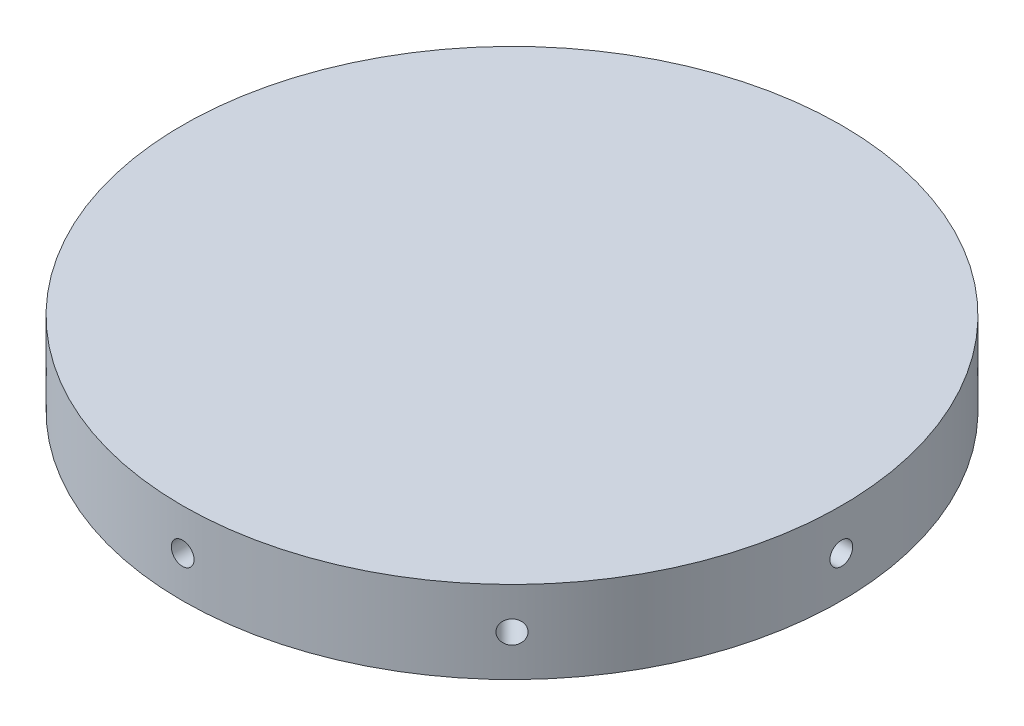
SolidWorks part; units mm, degrees
material "6061 Alloy"
ref_plane "Front Plane" through (0, 0, 0) normal (0, 0, 1) x (1, 0, 0)
ref_plane "Top Plane" through (0, 0, 0) normal (0, 1, 0) x (1, 0, 0)
ref_plane "Right Plane" through (0, 0, 0) normal (1, 0, 0) x (0, 0, -1)
sketch "Sketch1" plane through (0, 0, 0) normal (0, 1, 0) x (1, 0, 0)
  circle A0 centre (0, 0) radius 50.8
  dimension "D1" = 101.6
extrude "Boss-Extrude1" add sketch "Sketch1" along normal blind 12.7
ref_plane "Plane1" through (0, 0, 50.8) normal (0, 0, 1) x (1, 0, 0)
sketch "Sketch2" plane through (0, 0, 50.8) normal (0, 0, 1) x (1, 0, 0)
  line L0 (0, 0) -> (0, 12.7) construction
  line L1 (50.8, 12.7) -> (-50.8, 12.7) construction
  circle A0 centre (0, 6.35) radius 1.7526
  dimension "D1" = 3.5052
extrude "Cut-Extrude1" cut sketch "Sketch2" against normal blind 19.05
pattern_circular "CirPattern1" count 8 over 360 about axis through (0, 12.7, 0) along (0, -1, 0) of "Cut-Extrude1" reverse direction yes
